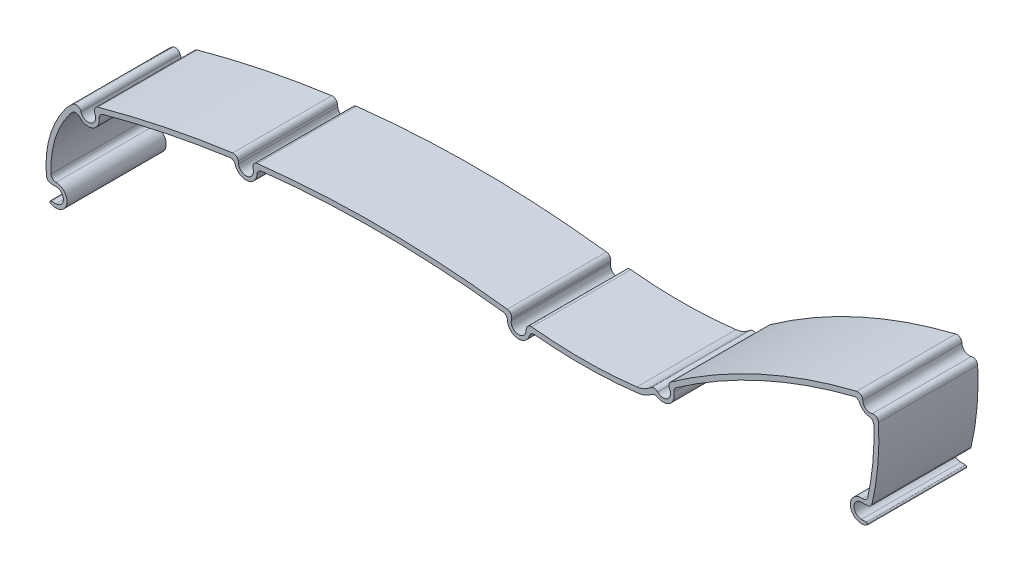
SolidWorks part; units mm, degrees
material "ｴﾎﾟｷｼ樹脂(充填剤なし)"
ref_plane "正面" through (0, 0, 0) normal (0, 0, 1) x (1, 0, 0)
ref_plane "平面" through (0, 0, 0) normal (0, 1, 0) x (1, 0, 0)
ref_plane "右側面" through (0, 0, 0) normal (1, 0, 0) x (0, 0, -1)
sketch "ｽｹｯﾁ1" plane through (0, 0, 0) normal (0, 0, 1) x (1, 0, 0)
  line L0 (152.9752, 59.7355) -> (155.8598, 58.9115) construction
  line L2 (-22.5, -19) -> (22.5, -19)
  line L21 (146, -0.0685) -> (146, 15.0697)
  circle A0 centre (152.9752, 59.7355) radius 3 construction
  arc A25 (145.1217, 33.8719) -> (159.4857, 98.9896) centre (52.35, 88.479) ccw
  arc A26 (159.4857, 98.9896) -> (155.8531, 101.6261) centre (156.5, 98.6967) ccw
  arc A27 (155.8531, 101.6261) -> (74.5652, 65.2106) centre (203.2901, -113.1988) ccw
  arc A28 (73.7195, 65.056) -> (74.5652, 65.2106) centre (73.98, 66.0215) ccw
  arc A29 (73.7195, 65.056) -> (74.5652, 65.2106) centre (73.98, 66.0215) ccw
  arc A30 (73.7195, 65.056) -> (69.9392, 62.246) centre (72.938, 62.1596) ccw
  arc A31 (73.7195, 65.056) -> (69.9392, 62.246) centre (72.938, 62.1596) ccw
  arc A32 (62.3481, 57.6959) -> (67.3326, 59.7624) centre (61.1527, 67.6242) ccw
  arc A33 (15.0718, 58.0612) -> (62.3481, 57.6959) centre (40.1338, 242.1889) ccw
  arc A34 (15.0718, 58.0612) -> (-159.8291, 45.3832) centre (-42.29, -363.3692) ccw
  arc A35 (-159.8291, 45.3832) -> (-168.029, 39.7531) centre (-155.4945, 30.2837) ccw
  arc A36 (-168.029, 39.7531) -> (-174.9177, 6.802) centre (-136.5587, 15.9784) ccw
  arc A37 (-174.9177, 6.802) -> (-172, 4.5) centre (-172, 7.5) ccw
  arc A38 (-128.5711, -10.4869) -> (-172, 4.5) centre (-172, -65.9175) ccw
  arc A39 (-128.5711, -10.4869) -> (-89, -16.1206) centre (-103.9017, 21) ccw
  arc A40 (-24.2684, -18.5879) -> (-89, -16.1206) centre (-59.3978, -89.8605) ccw
  arc A41 (-24.2684, -18.5879) -> (-22.5, -19) centre (-22.5, -15) ccw
  arc A42 (95.4808, -24.1793) -> (22.5, -19) centre (22.5, -535.7727) ccw
  arc A43 (95.4808, -24.1793) -> (100, -24.5) centre (100, 7.5) ccw
  arc A44 (100, -24.5) -> (140.9896, -3.1331) centre (100, 25.5) ccw
  arc A45 (146, -0.0685) -> (140.9896, -3.1331) centre (147, -7.3316) ccw
  arc A48 (69.5475, 61.4807) -> (69.9392, 62.246) centre (68.9396, 62.2747) ccw
  arc A49 (145.1217, 33.8719) -> (140.5409, 25.3936) centre (258.447, -32.8336) ccw
  arc A50 (155.8598, 58.9115) -> (159.4857, 98.9896) centre (52.35, 88.479) ccw
  arc A51 (159.4857, 98.9896) -> (155.8531, 101.6261) centre (156.5, 98.6967) ccw
  arc A52 (155.8531, 101.6261) -> (74.5652, 65.2106) centre (203.2901, -113.1988) ccw
  arc A53 (69.5475, 61.4807) -> (69.9392, 62.246) centre (68.9396, 62.2747) ccw
  arc A54 (69.5475, 61.4807) -> (67.3326, 59.7624) centre (203.2901, -113.1988) ccw
  arc A55 (69.5475, 61.4807) -> (67.3326, 59.7624) centre (203.2901, -113.1988) ccw
  arc A56 (140.5409, 25.3936) -> (146, 15.0697) centre (147, 22.2038) ccw
  arc A57 (62.3481, 57.6959) -> (67.3326, 59.7624) centre (61.1527, 67.6242) ccw
  arc A58 (15.0718, 58.0612) -> (62.3481, 57.6959) centre (40.1338, 242.1889) ccw
  arc A59 (15.0718, 58.0612) -> (-159.8291, 45.3832) centre (-42.29, -363.3692) ccw
  arc A60 (-159.8291, 45.3832) -> (-168.029, 39.7531) centre (-155.4945, 30.2837) ccw
  arc A61 (-168.029, 39.7531) -> (-174.9177, 6.802) centre (-136.5587, 15.9784) ccw
  dimension "D1" = 0
extrude "押し出し-薄板1" add sketch "ｽｹｯﾁ1" along normal up to surface (40 mm away) thin thin type one direction reverse wall 2
sketch "ｽｹｯﾁ2" plane through (0, 0, 0) normal (0, 0, 1) x (1, 0, 0)
  circle A0 centre (156.5, 98.6967) radius 3 construction
  circle A1 centre (152.9752, 59.7355) radius 3 construction
  circle A2 centre (72.938, 62.1596) radius 3 construction
  circle A3 centre (14.6672, 55.0886) radius 3 construction
  circle A4 centre (-95.3328, 55.6027) radius 3 construction
  circle A5 centre (-159, 42.5) radius 3 construction
  circle A6 centre (-172, 7.5) radius 3 construction
  circle A7 centre (156.5, 98.6967) radius 3
  circle A8 centre (152.9752, 59.7355) radius 3
  circle A9 centre (72.938, 62.1596) radius 3
  circle A10 centre (14.6672, 55.0886) radius 3
  circle A11 centre (-95.3328, 55.6027) radius 3
  circle A12 centre (-159, 42.5) radius 3
  circle A13 centre (-172, 7.5) radius 3
extrude "ﾎﾞｽ - 押し出し1" add sketch "ｽｹｯﾁ2" along normal through all
sketch "ｽｹｯﾁ3" plane through (0, 0, 40) normal (0, 0, 1) x (1, 0, 0)
  circle A0 centre (-172, 7.5) radius 4.5
  circle A1 centre (-159, 42.5) radius 4.5
  circle A2 centre (-95.3328, 55.6027) radius 4.5
  circle A3 centre (14.6672, 55.0886) radius 4.5
  circle A4 centre (72.938, 62.1596) radius 4.5
  circle A5 centre (156.5, 98.6967) radius 4.5
  circle A6 centre (152.9752, 59.7355) radius 4.5
  arc A37 (-168.029, 39.7531) -> (-174.9177, 6.802) centre (-136.5587, 15.9784) ccw
  arc A38 (-174.9177, 6.802) -> (-173.5323, 10.0791) centre (-172, 7.5) ccw
  arc A39 (-166.4332, 38.5475) -> (-173.5323, 10.0791) centre (-136.5587, 15.9784) ccw
  arc A40 (-161.9964, 42.3531) -> (-166.4332, 38.5475) centre (-155.4945, 30.2837) ccw
  arc A41 (-161.9964, 42.3531) -> (-156.5523, 44.2345) centre (-159, 42.5) ccw
  arc A42 (-98.2666, 56.2298) -> (-156.5523, 44.2345) centre (-42.29, -363.3692) ccw
  arc A43 (-98.2666, 56.2298) -> (-92.6479, 56.9411) centre (-95.3328, 55.6027) ccw
  arc A44 (11.9949, 56.452) -> (-92.6479, 56.9411) centre (-42.29, -363.3692) ccw
  arc A45 (11.9949, 56.452) -> (17.6, 55.72) centre (14.6672, 55.0886) ccw
  arc A46 (17.6, 55.72) -> (62.5872, 55.7103) centre (40.1338, 242.1889) ccw
  arc A47 (62.5872, 55.7103) -> (68.5686, 58.19) centre (61.1527, 67.6242) ccw
  arc A48 (70.7634, 59.8927) -> (68.5686, 58.19) centre (203.2901, -113.1988) ccw
  arc A49 (70.7634, 59.8927) -> (70.8745, 59.982) centre (68.9396, 62.2747) ccw
  arc A50 (70.8745, 59.982) -> (75.6179, 63.508) centre (72.938, 62.1596) ccw
  arc A51 (75.6179, 63.508) -> (75.7354, 63.5887) centre (73.98, 66.0215) ccw
  arc A52 (153.5202, 99.0439) -> (75.7354, 63.5887) centre (203.2901, -113.1988) ccw
  arc A53 (153.5202, 99.0439) -> (157.7346, 95.9625) centre (156.5, 98.6967) ccw
  arc A54 (154.6805, 62.2037) -> (157.7346, 95.9625) centre (52.35, 88.479) ccw
  arc A55 (154.6805, 62.2037) -> (155.8598, 58.9115) centre (152.9752, 59.7355) ccw
  arc A56 (155.8598, 58.9115) -> (159.4857, 98.9896) centre (52.35, 88.479) ccw
  arc A57 (159.4857, 98.9896) -> (155.8531, 101.6261) centre (156.5, 98.6967) ccw
  arc A58 (155.8531, 101.6261) -> (74.5652, 65.2106) centre (203.2901, -113.1988) ccw
  arc A59 (73.7195, 65.056) -> (74.5652, 65.2106) centre (73.98, 66.0215) ccw
  arc A60 (73.7195, 65.056) -> (69.9392, 62.246) centre (72.938, 62.1596) ccw
  arc A61 (69.5475, 61.4807) -> (69.9392, 62.246) centre (68.9396, 62.2747) ccw
  arc A62 (69.5475, 61.4807) -> (67.3326, 59.7624) centre (203.2901, -113.1988) ccw
  arc A63 (62.3481, 57.6959) -> (67.3326, 59.7624) centre (61.1527, 67.6242) ccw
  arc A64 (15.0718, 58.0612) -> (62.3481, 57.6959) centre (40.1338, 242.1889) ccw
  arc A65 (15.0718, 58.0612) -> (-159.8291, 45.3832) centre (-42.29, -363.3692) ccw
  arc A66 (-159.8291, 45.3832) -> (-168.029, 39.7531) centre (-155.4945, 30.2837) ccw
  arc A67 (-168.029, 39.7531) -> (-174.9177, 6.802) centre (-136.5587, 15.9784) ccw
  arc A68 (-174.9177, 6.802) -> (-173.5323, 10.0791) centre (-172, 7.5) ccw
  arc A69 (-166.4332, 38.5475) -> (-173.5323, 10.0791) centre (-136.5587, 15.9784) ccw
  arc A70 (-161.9964, 42.3531) -> (-166.4332, 38.5475) centre (-155.4945, 30.2837) ccw
  arc A71 (-161.9964, 42.3531) -> (-156.5523, 44.2345) centre (-159, 42.5) ccw
  arc A72 (-98.2666, 56.2298) -> (-156.5523, 44.2345) centre (-42.29, -363.3692) ccw
  arc A73 (-98.2666, 56.2298) -> (-92.6479, 56.9411) centre (-95.3328, 55.6027) ccw
  arc A74 (11.9949, 56.452) -> (-92.6479, 56.9411) centre (-42.29, -363.3692) ccw
  arc A75 (11.9949, 56.452) -> (17.6, 55.72) centre (14.6672, 55.0886) ccw
  arc A76 (17.6, 55.72) -> (62.5872, 55.7103) centre (40.1338, 242.1889) ccw
  arc A77 (62.5872, 55.7103) -> (68.5686, 58.19) centre (61.1527, 67.6242) ccw
  arc A78 (70.7634, 59.8927) -> (68.5686, 58.19) centre (203.2901, -113.1988) ccw
  arc A79 (70.7634, 59.8927) -> (70.8745, 59.982) centre (68.9396, 62.2747) ccw
  arc A80 (70.8745, 59.982) -> (75.6179, 63.508) centre (72.938, 62.1596) ccw
  arc A81 (75.6179, 63.508) -> (75.7354, 63.5887) centre (73.98, 66.0215) ccw
  arc A82 (153.5202, 99.0439) -> (75.7354, 63.5887) centre (203.2901, -113.1988) ccw
  arc A83 (153.5202, 99.0439) -> (157.7346, 95.9625) centre (156.5, 98.6967) ccw
  arc A84 (154.6805, 62.2037) -> (157.7346, 95.9625) centre (52.35, 88.479) ccw
  arc A85 (154.6805, 62.2037) -> (155.8598, 58.9115) centre (152.9752, 59.7355) ccw
  arc A86 (155.8598, 58.9115) -> (159.4857, 98.9896) centre (52.35, 88.479) ccw
  arc A87 (159.4857, 98.9896) -> (155.8531, 101.6261) centre (156.5, 98.6967) ccw
  arc A88 (155.8531, 101.6261) -> (74.5652, 65.2106) centre (203.2901, -113.1988) ccw
  arc A89 (73.7195, 65.056) -> (74.5652, 65.2106) centre (73.98, 66.0215) ccw
  arc A90 (73.7195, 65.056) -> (69.9392, 62.246) centre (72.938, 62.1596) ccw
  arc A91 (69.5475, 61.4807) -> (69.9392, 62.246) centre (68.9396, 62.2747) ccw
  arc A92 (69.5475, 61.4807) -> (67.3326, 59.7624) centre (203.2901, -113.1988) ccw
  arc A93 (62.3481, 57.6959) -> (67.3326, 59.7624) centre (61.1527, 67.6242) ccw
  arc A94 (15.0718, 58.0612) -> (62.3481, 57.6959) centre (40.1338, 242.1889) ccw
  arc A95 (15.0718, 58.0612) -> (-159.8291, 45.3832) centre (-42.29, -363.3692) ccw
  arc A96 (-159.8291, 45.3832) -> (-168.029, 39.7531) centre (-155.4945, 30.2837) ccw
  arc M31 (-168.029, 39.7531) -> (-174.9177, 6.802) centre (-136.5587, 15.9784) ccw
  arc M32 (-174.9177, 6.802) -> (-173.5323, 10.0791) centre (-172, 7.5) ccw
  arc M33 (-173.5323, 10.0791) -> (-166.4332, 38.5475) centre (-136.5587, 15.9784) cw
  arc M34 (-166.4332, 38.5475) -> (-161.9964, 42.3531) centre (-155.4945, 30.2837) cw
  arc M35 (-161.9964, 42.3531) -> (-156.5523, 44.2345) centre (-159, 42.5) ccw
  arc M36 (-156.5523, 44.2345) -> (-98.2666, 56.2298) centre (-42.29, -363.3692) cw
  arc M37 (-98.2666, 56.2298) -> (-92.6479, 56.9411) centre (-95.3328, 55.6027) ccw
  arc M38 (-92.6479, 56.9411) -> (11.9949, 56.452) centre (-42.29, -363.3692) cw
  arc M39 (11.9949, 56.452) -> (17.6, 55.72) centre (14.6672, 55.0886) ccw
  arc M40 (17.6, 55.72) -> (62.5872, 55.7103) centre (40.1338, 242.1889) ccw
  arc M42 (68.5686, 58.19) -> (70.7634, 59.8927) centre (203.2901, -113.1988) cw
  arc M43 (70.7634, 59.8927) -> (70.8745, 59.982) centre (68.9396, 62.2747) ccw
  arc M44 (70.8745, 59.982) -> (75.6179, 63.508) centre (72.938, 62.1596) ccw
  arc M45 (75.6179, 63.508) -> (75.7354, 63.5887) centre (73.98, 66.0215) ccw
  arc M46 (75.7354, 63.5887) -> (153.5202, 99.0439) centre (203.2901, -113.1988) cw
  arc M47 (153.5202, 99.0439) -> (157.7346, 95.9625) centre (156.5, 98.6967) ccw
  arc M48 (157.7346, 95.9625) -> (154.6805, 62.2037) centre (52.35, 88.479) cw
  arc M49 (154.6805, 62.2037) -> (155.8598, 58.9115) centre (152.9752, 59.7355) ccw
  arc M50 (155.8598, 58.9115) -> (159.4857, 98.9896) centre (52.35, 88.479) ccw
  dimension "D1" = 9
  dimension "D2" = 0
extrude "ﾎﾞｽ - 押し出し2" add sketch "ｽｹｯﾁ3" against normal through all contours A6 M48 M50 M49 | A5 M46 M48 M47 | A4 M42 M46 M45 M44 M43 | A3 M38 M40 M39 | A2 M36 M38 M37 | A1 M34 M36 M35 | A0 M31 M33 M32 region at (-173.3991, 3.3572, 40) region at (-162.6457, 41.8498, 40) region at (-99.0256, 56.0185, 40) region at (11.207, 56.4437, 40) region at (70.2831, 59.3943, 40) region at (154.6043, 96.1097, 40) region at (154.749, 62.9939, 40)
sketch "ｽｹｯﾁ4" plane through (0, 0, 40) normal (0, 0, 1) x (1, 0, 0)
  line L0 (-159, 42.5) -> (-159.8361, 45.3811) construction
  line L1 (-161.8811, 41.6639) -> (-162.7173, 44.545)
  line L2 (-156.1189, 43.3361) -> (-156.955, 46.2173)
  line L3 (-172, 7.5) -> (-176.5, 7.5) construction
  line L4 (-172, 4.5) -> (-176.5, 4.5)
  line L5 (-172, 10.5) -> (-176.5, 10.5)
  line L6 (-95.3328, 55.6027) -> (-95.7096, 58.579) construction
  line L7 (-98.3091, 55.2259) -> (-98.6859, 58.2022)
  line L8 (-92.3566, 55.9795) -> (-92.7334, 58.9558)
  line L9 (14.6672, 55.0886) -> (15.0718, 58.0612) construction
  line L10 (11.6946, 55.4932) -> (12.0992, 58.4658)
  line L11 (17.6397, 54.684) -> (18.0444, 57.6566)
  line L12 (72.938, 62.1596) -> (71.1482, 64.5673) construction
  line L13 (70.5303, 60.3699) -> (68.7406, 62.7776)
  line L14 (75.3456, 63.9494) -> (73.5559, 66.357)
  line L15 (156.5, 98.6967) -> (158.2622, 101.1246) construction
  line L16 (154.0721, 100.4589) -> (155.8343, 102.8868)
  line L17 (158.9279, 96.9345) -> (160.6901, 99.3624)
  line L18 (152.9752, 59.7355) -> (157.4752, 59.7355) construction
  line L19 (152.9752, 62.7355) -> (157.4752, 62.7355)
  line L20 (152.9752, 56.7355) -> (157.4752, 56.7355)
  line L21 (-99.8134, 56.0205) -> (-91.0978, 57.1239) construction
  arc A0 (15.0718, 58.0612) -> (-159.8291, 45.3832) centre (-42.29, -363.3692) ccw construction
  arc A1 (-159.8291, 45.3832) -> (-168.029, 39.7531) centre (-155.4945, 30.2837) ccw construction
  arc A2 (-161.8811, 41.6639) -> (-156.1189, 43.3361) centre (-159, 42.5) ccw
  arc A3 (-156.955, 46.2173) -> (-162.7173, 44.545) centre (-159.8361, 45.3811) ccw
  arc A4 (-172, 4.5) -> (-172, 10.5) centre (-172, 7.5) ccw
  arc A5 (-176.5, 10.5) -> (-176.5, 4.5) centre (-176.5, 7.5) ccw
  arc A6 (-98.3091, 55.2259) -> (-92.3566, 55.9795) centre (-95.3328, 55.6027) ccw
  arc A7 (-92.7334, 58.9558) -> (-98.6859, 58.2022) centre (-95.7096, 58.579) ccw
  arc A8 (15.0718, 58.0612) -> (62.3481, 57.6959) centre (40.1338, 242.1889) ccw construction
  arc A9 (11.6946, 55.4932) -> (17.6397, 54.684) centre (14.6672, 55.0886) ccw
  arc A10 (18.0444, 57.6566) -> (12.0992, 58.4658) centre (15.0718, 58.0612) ccw
  arc A11 (73.7195, 65.056) -> (69.9392, 62.246) centre (72.938, 62.1596) ccw construction
  arc A12 (70.5303, 60.3699) -> (75.3456, 63.9494) centre (72.938, 62.1596) ccw
  arc A13 (73.5559, 66.357) -> (68.7406, 62.7776) centre (71.1482, 64.5673) ccw
  arc A14 (159.4857, 98.9896) -> (155.8531, 101.6261) centre (156.5, 98.6967) ccw construction
  arc A15 (154.0721, 100.4589) -> (158.9279, 96.9345) centre (156.5, 98.6967) ccw
  arc A16 (160.6901, 99.3624) -> (155.8343, 102.8868) centre (158.2622, 101.1246) ccw
  arc A17 (155.0589, 63.7241) -> (156.7424, 62.1969) centre (152.9752, 59.7355) ccw construction
  arc A18 (152.9752, 62.7355) -> (152.9752, 56.7355) centre (152.9752, 59.7355) ccw
  arc A19 (157.4752, 56.7355) -> (157.4752, 62.7355) centre (157.4752, 59.7355) ccw
  arc A20 (-175.5786, 10.2283) -> (-173.7486, 11.6464) centre (-172, 7.5) ccw construction
  point P12 (-159.4181, 43.9406)
  point P19 (-174.25, 7.5)
  point P29 (-95.5212, 57.0909)
  point P37 (14.8695, 56.5749)
  point P48 (72.0431, 63.3635)
  point P59 (157.3811, 99.9106)
  point P70 (155.2252, 59.7355)
  dimension "D1" = 6
extrude "ｶｯﾄ - 押し出し2" cut sketch "ｽｹｯﾁ4" against normal through all
fillet "ﾌｨﾚｯﾄ1" radius 2 24 edges at (-173.7486, 11.6464, 20) (-155.0485, 44.6531, 20) (-99.8134, 56.0205, 20) (-91.0978, 57.1239, 20) (10.4465, 56.6493, 20) (19.1445, 55.5398, 20) (69.6787, 59.0569, 20) (76.8484, 64.3864, 20) (152, 98.6817, 20) (157.834, 94.399, 20) (155.0589, 63.7241, 20) (156.8765, 62.7355, 20) (159.5915, 97.8487, 20) (154.7384, 101.3769, 20) (74.4582, 65.1432, 20) (69.6428, 61.5638, 20) (18.0475, 57.6806, 20) (12.0977, 58.4553, 20) (-92.7321, 58.9453, 20) (-98.6846, 58.1917, 20) (-156.95, 46.2001, 20) (-162.6387, 44.2745, 20) (-175.6177, 10.5, 20) (-163.3861, 41.4939, 20)
fillet "ﾌｨﾚｯﾄ2" radius 0.5 2 edges at (156.3293, 56.7355, 20) (-175.3541, 4.5, 20)
